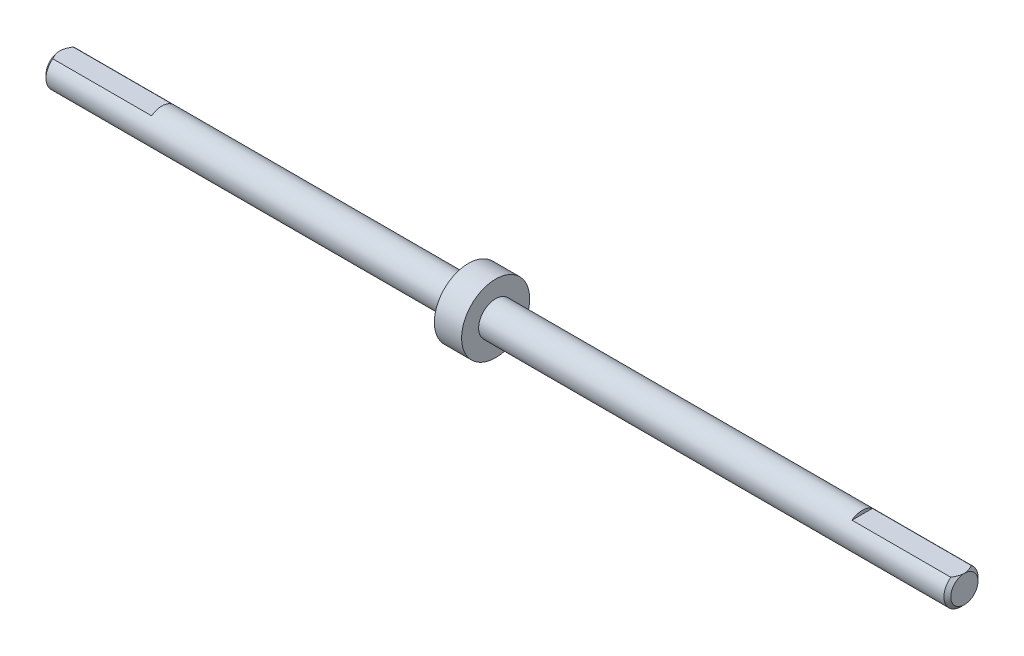
SolidWorks part; units mm, degrees
ref_plane "Front Plane" through (0, 0, 0) normal (0, 0, 1) x (1, 0, 0)
ref_plane "Top Plane" through (0, 0, 0) normal (0, 1, 0) x (1, 0, 0)
ref_plane "Right Plane" through (0, 0, 0) normal (1, 0, 0) x (0, 0, -1)
ref_plane "Plane1" through (0, 0, 0) normal (0, 0, -1) x (-1, 0, 0)
sketch "Sketch1" plane through (0, 0, 0) normal (0, 0, -1) x (-1, 0, 0)
  line L0 (-9, 5) -> (-9, 0)
  line L1 (-9, 0) -> (-5, 0)
  line L2 (-5, 0) -> (-5, 5)
  line L3 (-5, 5) -> (-9, 5)
  line L4 (-9, 0) -> (-5, 0) construction
revolve "Revolve1" add sketch "Sketch1" angle 360 about L4 reverse direction yes
sketch "Sketch2" plane through (9, 0, 0) normal (1, 0, 0) x (0, 0, -1)
  circle A0 centre (0, 0) radius 2.5
extrude "Boss-Extrude1" add sketch "Sketch2" along normal blind 68.8
sketch "Sketch3" plane through (77.8, 0, 0) normal (1, 0, 0) x (0, 0, -1)
  line L0 (-1.5, 2) -> (1.5, 2)
  arc A0 (1.5, 2) -> (-1.5, 2) centre (0, 0) ccw
extrude "Cut-Extrude1" cut sketch "Sketch3" against normal blind 15
sketch "Sketch4" plane through (5, 0, 0) normal (-1, 0, 0) x (0, 0, 1)
  circle A0 centre (0, 0) radius 2.5
extrude "Boss-Extrude2" add sketch "Sketch4" along normal blind 60
sketch "Sketch5" plane through (-55, 0, 0) normal (-1, 0, 0) x (0, 0, 1)
  line L0 (-1.5, 2) -> (1.5, 2)
  arc A0 (1.5, 2) -> (-1.5, 2) centre (0, 0) ccw
extrude "Cut-Extrude2" cut sketch "Sketch5" against normal blind 15
chamfer "Chamfer1" distance 0.5 angle 45 2 edges at (-55, -2.5, 0) (77.8, -2.5, 0)
